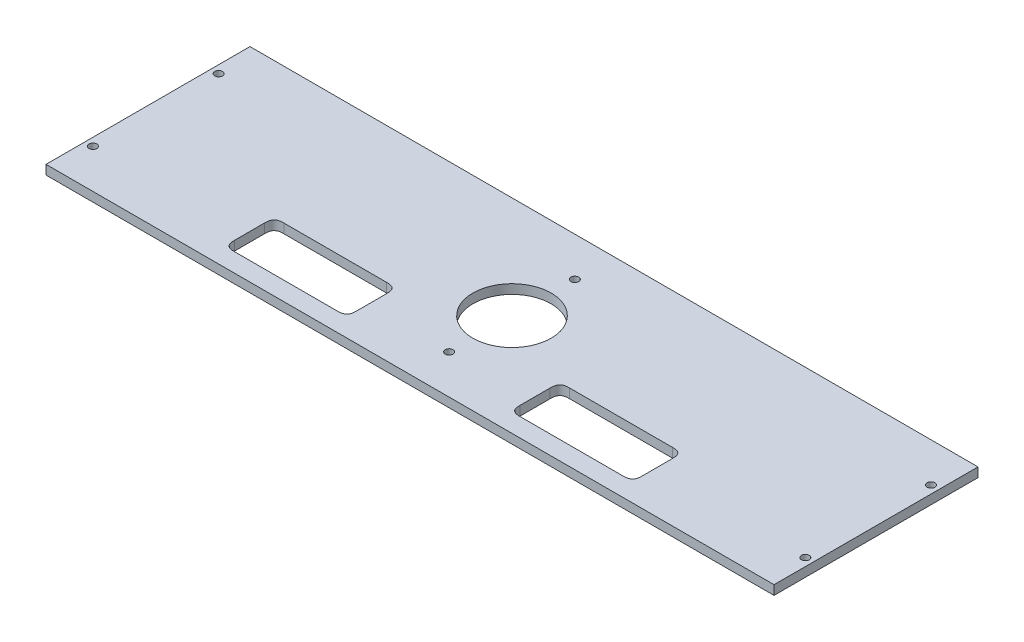
SolidWorks part; units mm, degrees
ref_plane "Front Plane" through (0, 0, 0) normal (0, 0, 1) x (1, 0, 0)
ref_plane "Top Plane" through (0, 0, 0) normal (0, 1, 0) x (1, 0, 0)
ref_plane "Right Plane" through (0, 0, 0) normal (1, 0, 0) x (0, 0, -1)
sketch "Sketch1" plane through (0, 0, 0) normal (0, 1, 0) x (1, 0, 0)
  line L1 (-113.8302, 59.2962) -> (258.1698, 59.2962)
  line L2 (-113.8302, 59.2962) -> (-113.8302, -44.9238)
  line L3 (-113.8302, -44.9238) -> (258.1698, -44.9238)
  line L4 (258.1698, 59.2962) -> (258.1698, -44.9238)
extrude "Boss-Extrude1" add sketch "Sketch1" along normal blind 4.7625 contours L1 L4 L3 L2
sketch "Sketch2" plane through (0, 4.7625, 0) normal (0, 1, 0) x (1, 0, 0)
  line L0 (-113.8302, 59.2962) -> (-109.8302, 59.2962)
  line L1 (-113.8302, 59.2962) -> (258.1698, 59.2962) construction
  line L2 (-113.8302, 59.2962) -> (-113.8302, 39.2962)
  line L3 (-113.8302, 59.2962) -> (-113.8302, -44.9238) construction
  line L4 (-109.8302, 59.2962) -> (-113.8302, 59.2962)
  line L5 (-109.8302, 59.2962) -> (-109.8302, 39.2962)
  line L6 (-113.8302, 59.2962) -> (-113.8302, 39.2962)
  line L7 (-109.8302, 39.2962) -> (-113.8302, 39.2962)
  line L8 (-113.8302, -44.9238) -> (-109.8302, -44.9238)
  line L9 (-113.8302, -44.9238) -> (-113.8302, -24.9238)
  line L10 (-109.8302, -44.9238) -> (-113.8302, -44.9238)
  line L11 (-109.8302, -44.9238) -> (-109.8302, -24.9238)
  line L12 (-113.8302, -44.9238) -> (-113.8302, -24.9238)
  line L13 (-109.8302, -24.9238) -> (-113.8302, -24.9238)
  line L14 (258.1698, -44.9238) -> (254.1698, -44.9238)
  line L15 (258.1698, -44.9238) -> (258.1698, -24.9238)
  line L16 (254.1698, -44.9238) -> (258.1698, -44.9238)
  line L17 (254.1698, -44.9238) -> (254.1698, -24.9238)
  line L18 (258.1698, -44.9238) -> (258.1698, -24.9238)
  line L19 (254.1698, -24.9238) -> (258.1698, -24.9238)
  line L20 (-113.8302, -44.9238) -> (258.1698, -44.9238) construction
  line L22 (255.0869, -37.1853) -> (259.0869, -37.1853)
  line L23 (255.0869, -37.1853) -> (255.0869, -41.1853)
  line L24 (259.0869, -37.1853) -> (255.0869, -37.1853)
  line L25 (259.0869, -37.1853) -> (259.0869, -41.1853)
  line L26 (255.0869, -37.1853) -> (255.0869, -41.1853)
  line L27 (259.0869, -41.1853) -> (255.0869, -41.1853)
  line L28 (258.1698, 59.2962) -> (254.1698, 59.2962)
  line L29 (258.1698, 59.2962) -> (258.1698, 39.2962)
  line L30 (254.1698, 59.2962) -> (258.1698, 59.2962)
  line L31 (254.1698, 59.2962) -> (254.1698, 39.2962)
  line L32 (258.1698, 59.2962) -> (258.1698, 39.2962)
  line L33 (254.1698, 39.2962) -> (258.1698, 39.2962)
  circle A0 centre (-109.8302, 39.2962) radius 2
  circle A1 centre (-109.8302, -24.9238) radius 2
  circle A2 centre (254.1698, -24.9238) radius 2
  circle A3 centre (259.0869, -41.1853) radius 2
  circle A4 centre (254.1698, 39.2962) radius 2
extrude "Cut-Extrude1" cut sketch "Sketch2" against normal blind 10 contours L7 A0 L5 | L5 A0 L7 | L33 A4 L31 | L31 A4 L33 | A1 | A2 region at (-109.5472, 4.7625, -39.0132) region at (-110.679, 4.7625, -40.145) region at (255.0186, 4.7625, -40.145) region at (253.8869, 4.7625, -39.0132)
sketch "Sketch3" plane through (0, 4.7625, 0) normal (0, 1, 0) x (1, 0, 0)
  line L0 (-113.8302, 59.2962) -> (-113.8302, 39.2962)
  line L1 (-113.8302, 59.2962) -> (-113.8302, -44.9238) construction
  line L2 (-113.8302, 39.2962) -> (258.1698, 39.2962)
  line L3 (258.1698, 59.2962) -> (258.1698, -44.9238) construction
  line L4 (-113.8302, -44.9238) -> (-113.8302, -24.9238)
  line L5 (-113.8302, -24.9238) -> (258.1698, -24.9238)
  circle A0 centre (72.1698, 39.2962) radius 2
  circle A1 centre (72.1698, -24.9238) radius 2
extrude "Cut-Extrude2" cut sketch "Sketch3" against normal blind 10 contours A1 | A0
sketch "Sketch4" plane through (0, 4.7625, 0) normal (0, 1, 0) x (1, 0, 0)
  line L0 (72.1698, 39.2962) -> (72.1698, -24.9238)
  circle A0 centre (72.1698, 7.1862) radius 20
extrude "Cut-Extrude3" cut sketch "Sketch4" against normal blind 26 contours L0 A0 | L0 A0 region at (80.6581, 4.7625, -7.1862) region at (63.6816, 4.7625, -7.1862)
sketch "Sketch5" plane through (0, 4.7625, 0) normal (0, 1, 0) x (1, 0, 0)
  line L0 (72.1698, -12.8138) -> (72.1698, -22.9238)
  line L1 (30.4087, -10.1184) -> (-32.0471, -10.1184)
  line L2 (30.4087, -10.1184) -> (30.4087, -35.4154)
  line L3 (30.4087, -35.4154) -> (-32.0471, -35.4154)
  line L4 (-32.0471, -10.1184) -> (-32.0471, -35.4154)
  line L5 (113.9309, -35.4154) -> (176.3868, -35.4154)
  line L6 (176.3868, -10.1184) -> (176.3868, -35.4154)
  line L7 (113.9309, -10.1184) -> (176.3868, -10.1184)
  line L8 (113.9309, -10.1184) -> (113.9309, -35.4154)
  circle A0 centre (72.1698, 7.1862) radius 20 construction
  circle A1 centre (72.1698, -24.9238) radius 2 construction
extrude "Cut-Extrude4" cut sketch "Sketch5" against normal blind 10 contours L1 L4 L3 L2 | L7 L8 L5 L6 region at (-0.8192, 4.7625, 22.7669) region at (145.1588, 4.7625, 22.7669)
fillet "Fillet2" radius 5 8 edges at (176.3868, 2.3813, 35.4154) (176.3868, 2.3813, 10.1184) (113.9309, 2.3813, 10.1184) (113.9309, 2.3813, 35.4154) (30.4087, 2.3813, 35.4154) (30.4087, 2.3813, 10.1184) (-32.0471, 2.3813, 10.1184) (-32.0471, 2.3813, 35.4154) curvature continuous yes
